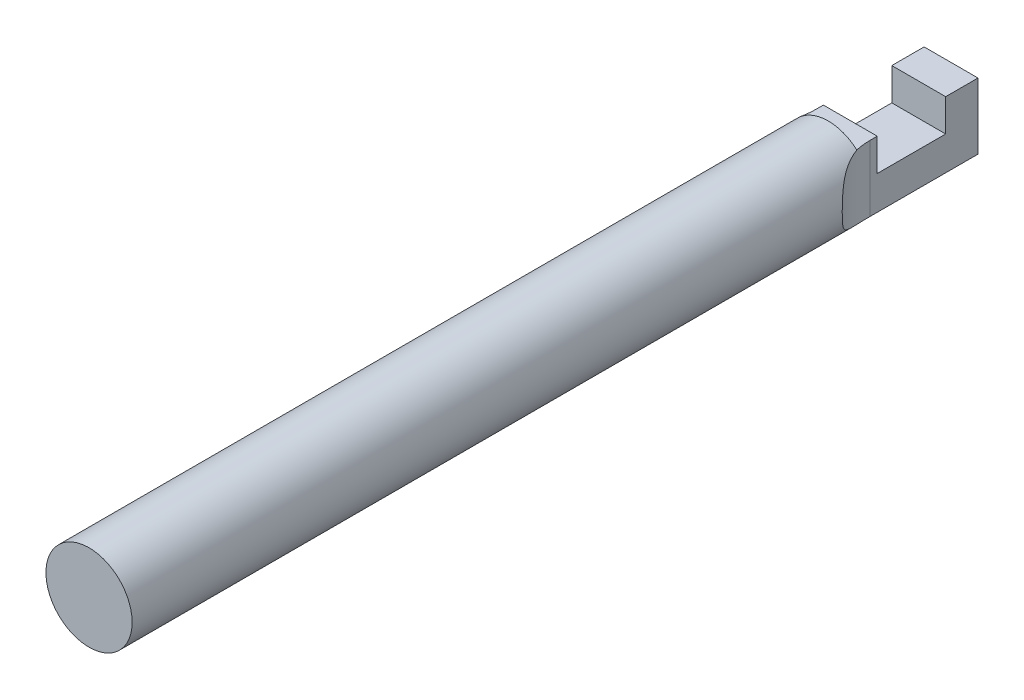
SolidWorks part; units mm, degrees
material "Alloy Steel"
ref_plane "Front" through (0, 0, 0) normal (0, 0, 1) x (1, 0, 0)
ref_plane "Top" through (0, 0, 0) normal (0, 1, 0) x (1, 0, 0)
ref_plane "Right" through (0, 0, 0) normal (1, 0, 0) x (0, 0, -1)
ref_axis "X" through (-80.9, 0, 0) along (1, 0, 0)
ref_axis "Y" through (0, -50, 0) along (0, 1, 0)
ref_axis "Z" through (0, 0, -80.9) along (0, 0, 1)
sketch "Sketch1" plane through (0, 0, 0) normal (1, 0, 0) x (0, 0, -1)
  line L0 (0, 0) -> (0, 2)
  line L1 (-40, 2) -> (-40, 0)
  line L2 (-40, 0) -> (0, 0)
  line L3 (-40, 2) -> (0, 2)
  line L4 (0.7212, 0) -> (9.8841, 0) construction
  dimension "D1" = 4
  dimension "D2" = 40
revolve "Revolve1" add sketch "Sketch1" angle 360 about L4
sketch "Sketch2" plane through (0, 0, 0) normal (0, 1, 0) x (1, 0, 0)
  line L0 (-1.25, 0) -> (-1.25, -5)
  line L1 (2, 0) -> (-2, 0) construction
  line L2 (1.25, 0) -> (1.25, -5)
  line L3 (4.425, -8.175) -> (4.425, 0)
  line L4 (4.425, 0) -> (1.25, 0)
  line L5 (-1.25, 0) -> (-4.425, 0)
  line L6 (-4.425, 0) -> (-4.425, -8.175)
  line L7 (0, 8.3405) -> (0, 0) construction
  arc A0 (-1.25, -5) -> (-4.425, -8.175) centre (-4.425, -5) cw
  arc A1 (1.25, -5) -> (4.425, -8.175) centre (4.425, -5) ccw
  dimension "D1" = 3.175
  dimension "D2" = 2.5
  dimension "D3" = 5
extrude "Cut-Extrude1" cut sketch "Sketch2" along normal through all both and the other way through all
sketch "Sketch3" plane through (0, 0, 0) normal (0, 1, 0) x (1, 0, 0)
  line L0 (-2, 0) -> (-2, -5.7)
  line L1 (-2, -5.7) -> (2, -5.7)
  line L2 (2, -5.7) -> (2, 0)
  line L3 (2, 0) -> (-2, 0)
  dimension "D1" = 4
  dimension "D2" = 5.7
extrude "Cut-Extrude2" cut sketch "Sketch3" along normal through all from offset 1.5
sketch "Sketch4" plane through (0, 0, 0) normal (0, 1, 0) x (1, 0, 0)
  line L0 (-1.25, -1.5) -> (1.25, -1.5)
  line L1 (-1.25, 0) -> (-1.25, -5) construction
  line L2 (1.25, -5) -> (1.25, 0) construction
  line L3 (1.25, -1.5) -> (1.25, -4.675)
  line L4 (1.25, -4.675) -> (-1.25, -4.675)
  line L6 (-1.25, -4.675) -> (-1.25, -1.5)
  line L7 (1.25, 0) -> (-1.25, 0) construction
  dimension "D1" = 1.5
  dimension "D2" = 3.175
extrude "Cut-Extrude3" cut sketch "Sketch4" along normal through all
